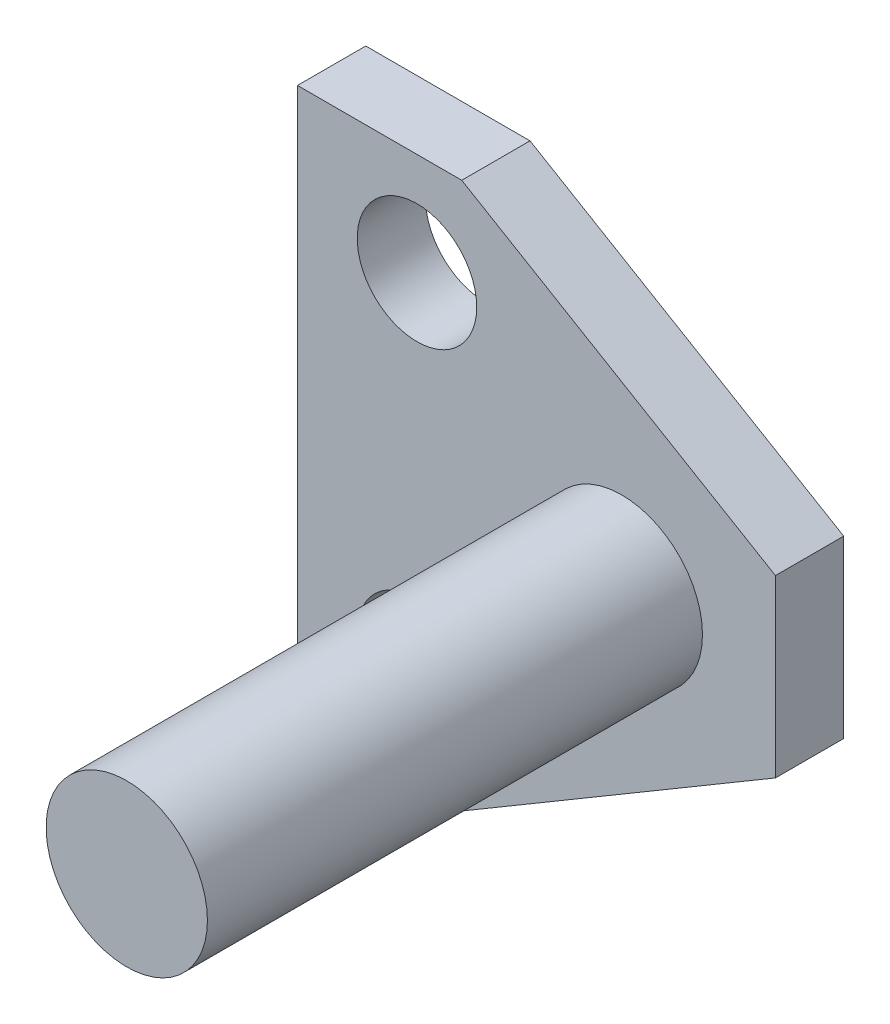
SolidWorks part; units mm, degrees
ref_plane "Front Plane" through (0, 0, 0) normal (0, 0, 1) x (1, 0, 0)
ref_plane "Top Plane" through (0, 0, 0) normal (0, 1, 0) x (1, 0, 0)
ref_plane "Right Plane" through (0, 0, 0) normal (1, 0, 0) x (0, 0, -1)
sketch "Sketch1" plane through (0, 0, 0) normal (0, 0, 1) x (1, 0, 0)
  line L0 (0, 0) -> (-6, 0) construction
  line L1 (-6, 5) -> (-6, -5) construction
  line L2 (-9.5, -8) -> (-9.5, 8)
  line L3 (-9.5, 8) -> (-4.6882, 8)
  line L4 (-4.6882, 8) -> (4.5, 2.567)
  line L5 (4.5, 2.567) -> (4.5, -2.567)
  line L6 (4.5, -2.567) -> (-4.6882, -8)
  line L7 (-4.6882, -8) -> (-9.5, -8)
  circle A0 centre (-6, -5) radius 1.75
  circle A1 centre (-6, 5) radius 1.75
  circle A2 centre (0, 0) radius 2.3625
  point P6 (-6, 0)
  dimension "D3" = 3.5
  dimension "D4" = 4.725
  dimension "D5" = 4.5
  dimension "D7" = 3.5
  dimension "D8" = 3
  dimension "D1" = 6
  dimension "D2" = 10
  dimension "D6" = 4.5
  dimension "D9" = 3.25
extrude "Boss-Extrude1" add sketch "Sketch1" along normal blind 2
extrude "Boss-Extrude2" add sketch "Sketch1<2>" along normal blind 16.5 contours A2 region at (0, 0, 0)
sketch "Sketch1<2>" plane through (0, 0, 0) normal (0, 0, 1) x (1, 0, 0) same geometry as "Sketch1"
